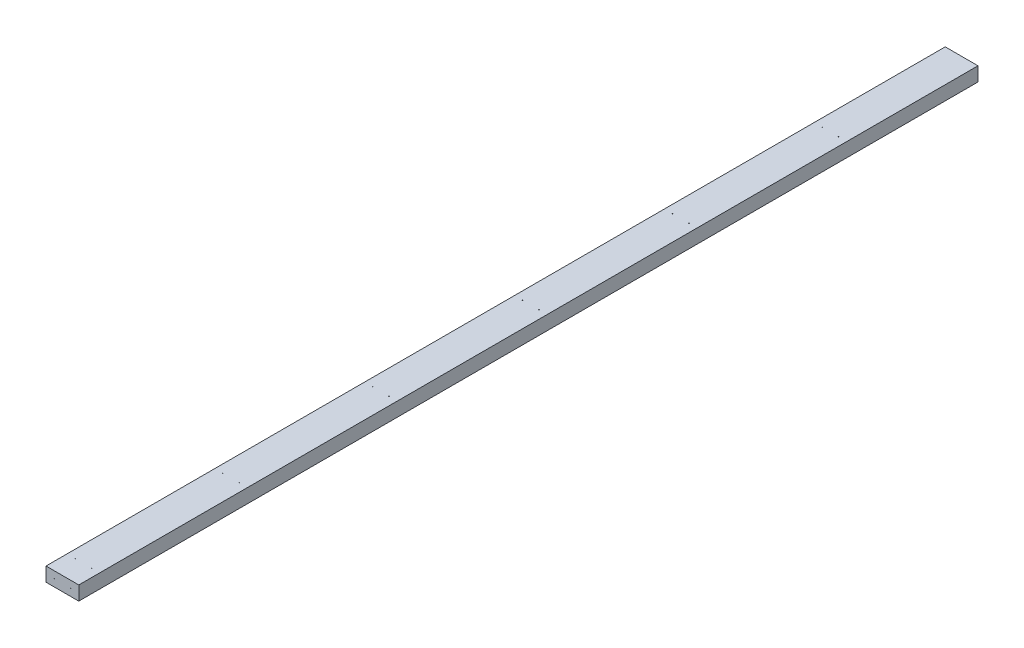
SolidWorks part; units mm, degrees
material "Pine"
ref_plane "Front Plane" through (0, 0, 0) normal (0, 0, 1) x (1, 0, 0)
ref_plane "Top Plane" through (0, 0, 0) normal (0, 1, 0) x (1, 0, 0)
ref_plane "Right Plane" through (0, 0, 0) normal (1, 0, 0) x (0, 0, -1)
sketch "Sketch1" plane through (0, 0, 0) normal (0, 0, 1) x (1, 0, 0)
  line L0 (0, 19.05) -> (44.45, 19.05) construction
  line L1 (0, 0) -> (88.9, 0)
  line L2 (0, 0) -> (0, 38.1)
  line L3 (0, 38.1) -> (88.9, 38.1)
  line L4 (88.9, 0) -> (88.9, 38.1)
  line L5 (44.45, 19.05) -> (88.9, 19.05) construction
  circle A0 centre (22.225, 19.05) radius 0.8763
  circle A1 centre (66.675, 19.05) radius 0.8763
  dimension "D3" = 1.7526
  dimension "D4" = 1.7526
  dimension "D1" = 88.9
  dimension "D2" = 38.1
extrude "Boss-Extrude1" add sketch "Sketch1" along normal blind 2438.4
sketch "Sketch3" plane through (0, 0, 0) normal (0, -1, 0) x (1, 0, 0)
  line L0 (0, 355.6) -> (44.45, 355.6) construction
  line L1 (0, 2438.4) -> (0, 0) construction
  line L2 (44.45, 355.6) -> (88.9, 355.6) construction
  line L3 (88.9, 2438.4) -> (88.9, 0) construction
  line L4 (0, 0) -> (88.9, 0) construction
  circle A0 centre (22.225, 355.6) radius 0.8763
  circle A1 centre (66.675, 355.6) radius 0.8763
  dimension "D2" = 1.7526
  dimension "D1" = 355.6
extrude "Cut-Extrude1" cut sketch "Sketch3" against normal up to surface (38.1 mm away) up to face at (44.45, 38.1, 1219.2)
pattern_linear "LPattern1" count 5 spacing 406.4 along (0, 0, 1) of "Cut-Extrude1"
sketch "Sketch4" plane through (0, 0, 0) normal (0, -1, 0) x (1, 0, 0)
  line L0 (44.45, 2381.25) -> (88.9, 2381.25) construction
  line L2 (88.9, 2438.4) -> (88.9, 0) construction
  line L3 (0, 2438.4) -> (88.9, 2438.4) construction
  line L4 (44.45, 2381.25) -> (0, 2381.25) construction
  line L5 (0, 2438.4) -> (0, 0) construction
  circle A0 centre (22.225, 2381.25) radius 0.8763
  circle A1 centre (66.675, 2381.25) radius 0.8763
  dimension "D2" = 1.7526
  dimension "D1" = 57.15
extrude "Cut-Extrude2" cut sketch "Sketch4" against normal up to surface (38.1 mm away) up to face at (66.675, 38.1, 1980.3237)
equation "\"length\"= 1219.2 * 2"
equation "\"D1@Boss-Extrude1\"=\"length\""
